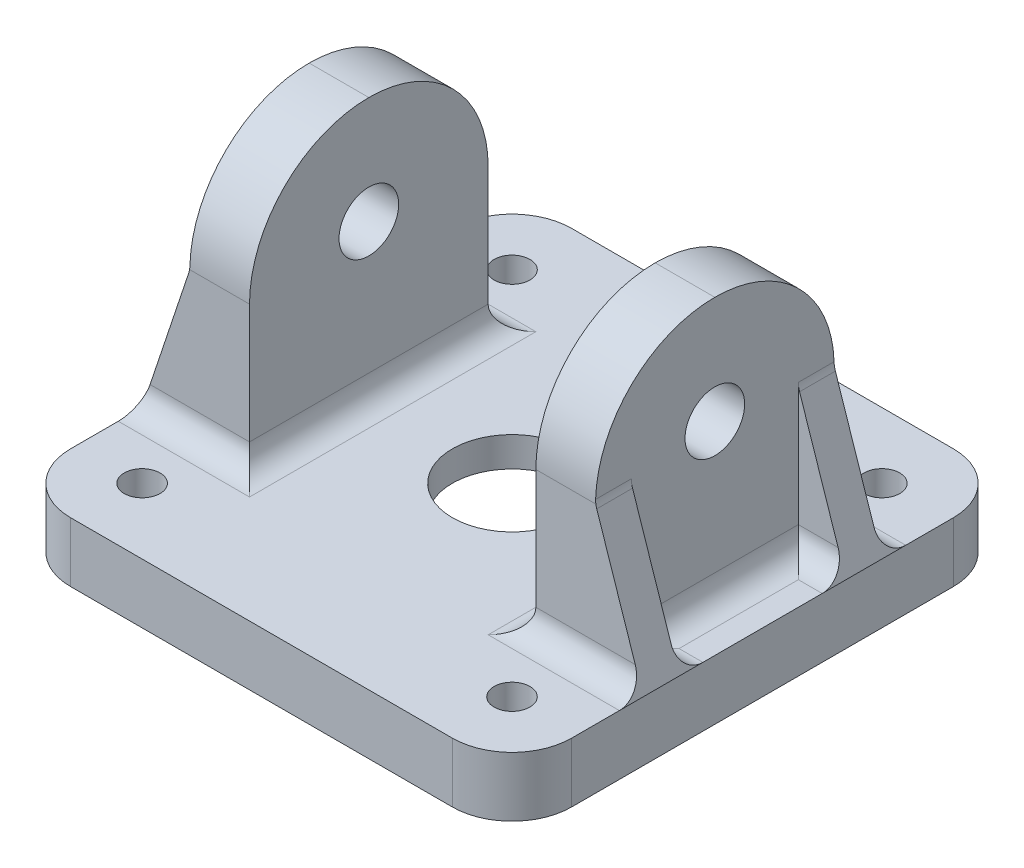
SolidWorks part; units mm, degrees
ref_plane "Front Plane" through (0, 0, 0) normal (0, 0, 1) x (1, 0, 0)
ref_plane "Top Plane" through (0, 0, 0) normal (0, 1, 0) x (1, 0, 0)
ref_plane "Right Plane" through (0, 0, 0) normal (1, 0, 0) x (0, 0, -1)
sketch "Sketch1" plane through (0, 0, 0) normal (0, 1, 0) x (1, 0, 0)
  line L1 (-21, 21) -> (21, 21)
  line L2 (-21, 21) -> (-21, -21)
  line L3 (-21, -21) -> (21, -21)
  line L4 (21, 21) -> (21, -21)
  line L5 (-21, 21) -> (21, -21) construction
  line L6 (-21, -21) -> (21, 21) construction
  circle A0 centre (-15.5, 15.5) radius 1.5
  circle A1 centre (15.5, 15.5) radius 1.5
  circle A2 centre (15.5, -15.5) radius 1.5
  circle A3 centre (-15.5, -15.5) radius 1.5
  point P0 (0, 0)
  point P17 (0, 0)
  dimension "D3" = 15.5
  dimension "D4" = 15.5
  dimension "D5" = 3
  dimension "D1" = 42
  dimension "D2" = 42
  dimension "D6" = 4
extrude "Boss-Extrude1" add sketch "Sketch1" along normal blind 5
sketch "Sketch2" plane through (0, 0, 0) normal (0, 1, 0) x (1, 0, 0)
  line L0 (0, -11) -> (0, 11) construction
  line L1 (-17, 10) -> (-12, 10)
  line L2 (-17, 10) -> (-17, -10)
  line L3 (-17, -10) -> (-12, -10)
  line L4 (-12, 10) -> (-12, -10)
  line L5 (12, 10) -> (12, -10)
  line L6 (17, -10) -> (12, -10)
  line L7 (17, 10) -> (17, -10)
  line L8 (17, 10) -> (12, 10)
  dimension "D1" = 5
  dimension "D2" = 12
  dimension "D3" = 20
  dimension "D4" = 10
extrude "Boss-Extrude2" add sketch "Sketch2" along normal blind 27
sketch "Sketch3" plane through (0, 0, 0) normal (1, 0, 0) x (0, 0, -1)
  circle A0 centre (0, 18) radius 2.5
  dimension "D1" = 5
  dimension "D2" = 18
extrude "Cut-Extrude1" cut sketch "Sketch3" against normal through all both and the other way through all
fillet "Fillet1" radius 10 4 edges at (-14.5, 27, 10) (-14.5, 27, -10) (14.5, 27, -10) (14.5, 27, 10)
fillet "Fillet2" radius 5 4 edges at (-21, 2.5, -21) (21, 2.5, -21) (-21, 2.5, 21) (21, 2.5, 21)
sketch "Sketch4" plane through (0, 0, 0) normal (0, 1, 0) x (1, 0, 0)
  circle A0 centre (0, 0) radius 11.25
  dimension "D1" = 22.5
extrude "Cut-Extrude2" cut sketch "Sketch4" along normal blind 2.5
sketch "Sketch5" plane through (0, 0, 0) normal (0, 1, 0) x (1, 0, 0)
  circle A0 centre (0, 0) radius 5
  dimension "D1" = 10
extrude "Cut-Extrude3" cut sketch "Sketch5" along normal blind 10
sketch "Sketch6" plane through (0, 0, 0) normal (0, 1, 0) x (1, 0, 0)
  line L0 (-21, 16) -> (-21, -16) construction
  line L1 (-17, 10) -> (-21, 10)
  line L2 (-17, 10) -> (-17, 7)
  line L3 (-17, 7) -> (-21, 7)
  line L4 (-21, 10) -> (-21, 7)
  line L5 (-14.85, 0) -> (14.85, 0) construction
  line L6 (-21, -10) -> (-21, -7)
  line L7 (-17, -7) -> (-21, -7)
  line L8 (-17, -10) -> (-17, -7)
  line L9 (-17, -10) -> (-21, -10)
  line L10 (0, -14.85) -> (0, 14.85) construction
  line L11 (17, -10) -> (21, -10)
  line L12 (17, -10) -> (17, -7)
  line L13 (17, -7) -> (21, -7)
  line L14 (21, -10) -> (21, -7)
  line L15 (21, 10) -> (21, 7)
  line L16 (17, 7) -> (21, 7)
  line L17 (17, 10) -> (17, 7)
  line L18 (17, 10) -> (21, 10)
  dimension "D1" = 3
extrude "Boss-Extrude3" add sketch "Sketch6" along normal blind 17
sketch "Sketch7" plane through (0, 0, 0) normal (0, 0, 1) x (1, 0, 0)
  line L0 (-17, 17) -> (-21, 5)
  line L1 (-21, 5) -> (-21, 17)
  line L2 (-21, 17) -> (-17, 17)
  line L3 (17, 17) -> (21, 17)
  line L4 (21, 17) -> (21, 5)
  line L5 (21, 5) -> (17, 17)
extrude "Cut-Extrude4" cut sketch "Sketch7" against normal through all both and the other way through all
fillet "Fillet3" radius 2 16 edges at (16.5, 5, 10) (17, 5, 0) (16.5, 5, -10) (-16.5, 5, -10) (-16.5, 5, 10) (-17, 5, 0) (12, 5, 0) (-12, 5, 0) (-17, 17, -8.5) (-17, 17, 8.5) (17, 17, -8.5) (17, 17, 8.5) (19, 5, -7) (19, 5, 7) (-19, 5, 7) (-19, 5, -7)
